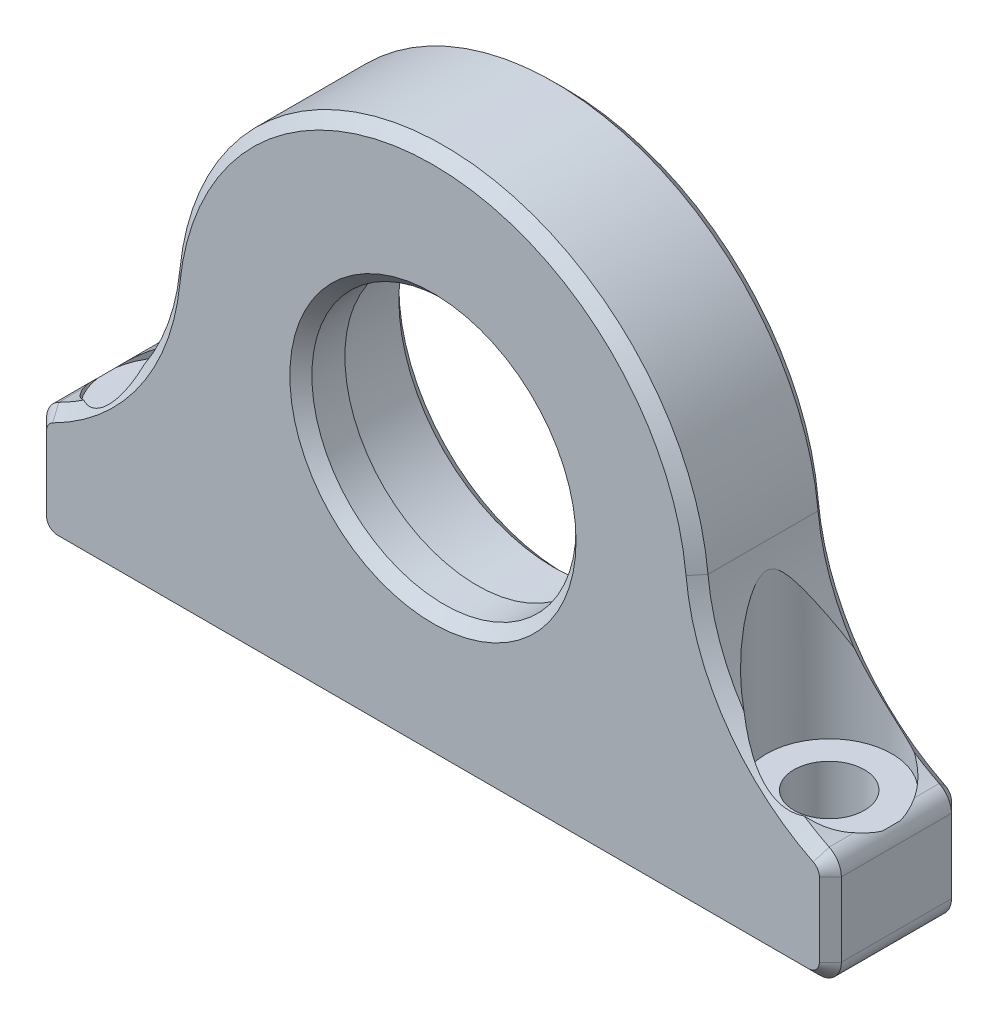
SolidWorks part; units mm, degrees
ref_plane "Front Plane" through (0, 0, 0) normal (0, 0, 1) x (1, 0, 0)
ref_plane "Top Plane" through (0, 0, 0) normal (0, 1, 0) x (1, 0, 0)
ref_plane "Right Plane" through (0, 0, 0) normal (1, 0, 0) x (0, 0, -1)
sketch "Sketch1" plane through (0, 0, 0) normal (0, 0, 1) x (1, 0, 0)
  line L0 (-18.05, -12.05) -> (-18.05, -7.05)
  line L1 (-18.05, -7.05) -> (-9.7724, -7.05)
  line L2 (-18.05, -12.05) -> (18.05, -12.05)
  line L3 (18.05, -12.05) -> (18.05, -7.05)
  line L4 (18.05, -7.05) -> (9.7724, -7.05)
  line L5 (-12.05, -1000) -> (-12.05, 49000) construction
  circle A0 centre (0, 0) radius 7.05
  arc A1 (-9.7724, -7.05) -> (9.7724, -7.05) centre (0, 0) cw
  point P5 (0, -12.05)
  point P9 (0, -7.05)
  dimension "D1" = 14.1
  dimension "D2" = 5
  dimension "D3" = 6
  dimension "D4" = 5
  dimension "D5" = 5
extrude "Boss-Extrude1" add sketch "Sketch1" along normal mid plane 4
sketch "Sketch2" plane through (0, 0, 2) normal (0, 0, 1) x (1, 0, 0)
  line L5 (-18.05, -12.05) -> (18.05, -12.05)
  line L6 (18.05, -12.05) -> (18.05, -7.05)
  line L7 (18.05, -7.05) -> (9.7724, -7.05)
  line L8 (-9.7724, -7.05) -> (-18.05, -7.05)
  line L9 (-18.05, -7.05) -> (-18.05, -12.05)
  line L10 (-18.05, -12.05) -> (18.05, -12.05)
  line L11 (18.05, -12.05) -> (18.05, -7.05)
  line L12 (18.05, -7.05) -> (9.7724, -7.05)
  line L13 (-9.7724, -7.05) -> (-18.05, -7.05)
  line L14 (-18.05, -7.05) -> (-18.05, -12.05)
  circle A0 centre (0, 0) radius 6
  arc A1 (9.7724, -7.05) -> (-9.7724, -7.05) centre (0, 0) ccw
  arc A2 (9.7724, -7.05) -> (-9.7724, -7.05) centre (0, 0) ccw
  dimension "D2" = 12
  dimension "D1" = 0
extrude "Boss-Extrude2" add sketch "Sketch2" along normal blind 2
fillet "Fillet1" radius 10 2 edges at (9.7724, -7.05, 1) (-9.7724, -7.05, 1)
ref_plane "Plane1" through (0, -7.05, 0) normal (0, -1, 0) x (-1, 0, 0)
fillet "Fillet2" radius 1 4 edges at (18.05, -12.05, 1) (18.05, -7.05, 1) (-18.05, -12.05, 1) (-18.05, -7.05, 1)
chamfer "Chamfer1" distance 0.5 angle 45 22 edges at (6, 0, 4) (-17.7571, -11.7571, 4) (-18.05, -9.3703, 4) (-17.9, -7.1638, 4) (-13.7128, -3.5182, 4) (0, 12.05, 4) (13.7128, -3.5182, 4) (17.9, -7.1638, 4) (18.05, -9.3703, 4) (17.7571, -11.7571, 4) (0, -12.05, 4) (7.05, 0, -2) (17.9, -7.1638, -2) (13.7128, -3.5182, -2) (0, 12.05, -2) (-13.7128, -3.5182, -2) (-17.9, -7.1638, -2) (-18.05, -9.3703, -2) (-17.7571, -11.7571, -2) (0, -12.05, -2) (17.7571, -11.7571, -2) (18.05, -9.3703, -2)
sketch "Sketch3" plane through (0, -7.05, 0) normal (0, -1, 0) x (-1, 0, 0)
  line L0 (18.05, 2) -> (11.9439, 2) construction
  line L1 (18.05, 2) -> (11.9439, 2)
  line L2 (18.05, -4) -> (18.05, 2) construction
  circle A0 centre (14.9969, -1) radius 1.6
  circle A1 centre (14.9969, -1) radius 2.85
  point P5 (14.9969, 2)
  point P9 (18.05, -1)
  dimension "D1" = 3.2
  dimension "D2" = 5.7
extrude "Cut-Extrude1" cut sketch "Sketch3" against normal through all contours A1 A0 | A0 region at (-14.9969, -7.05, 1) region at (-12.2275, -7.05, 1)
sketch "Sketch4" plane through (0, -7.05, 0) normal (0, 1, 0) x (1, 0, 0)
  circle A0 centre (-14.9969, -1) radius 1.6
  dimension "D1" = 3.2
extrude "Cut-Extrude2" cut sketch "Sketch4" against normal through all
mirror "Mirror1" about plane through (0, 0, 0) normal (1, 0, 0) of "Cut-Extrude2", "Cut-Extrude1"
